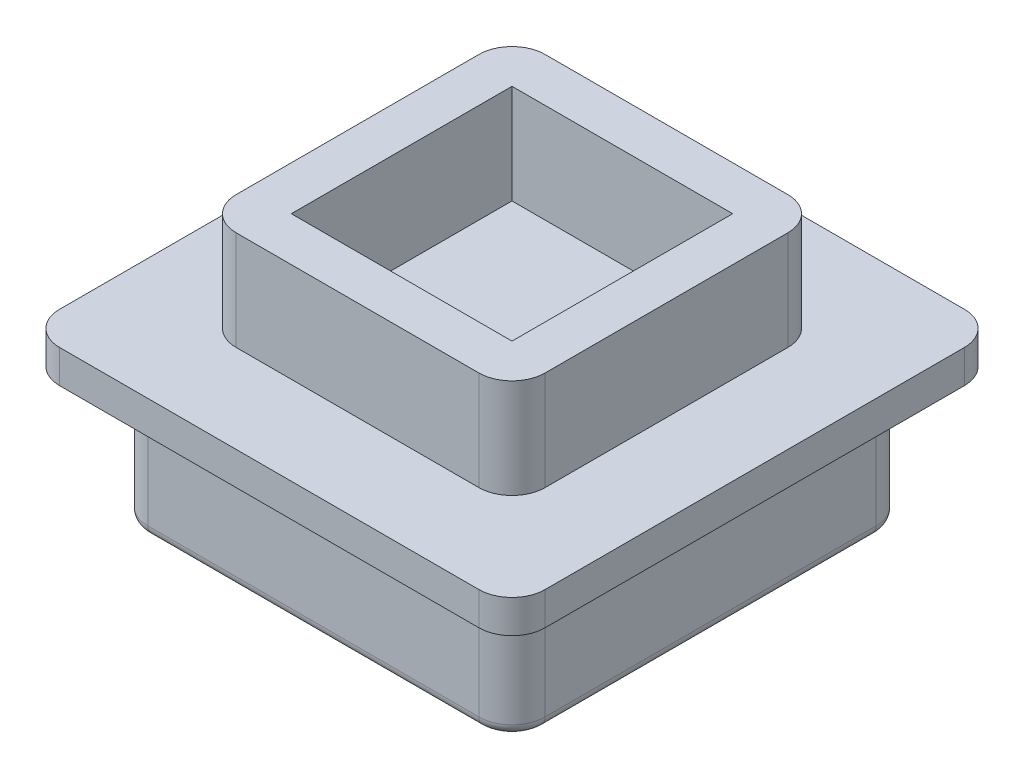
SolidWorks part; units mm, degrees
ref_plane "Front Plane" through (0, 0, 0) normal (0, 0, 1) x (1, 0, 0)
ref_plane "Top Plane" through (0, 0, 0) normal (0, 1, 0) x (1, 0, 0)
ref_plane "Right Plane" through (0, 0, 0) normal (1, 0, 0) x (0, 0, -1)
sketch "Sketch1" plane through (0, 0, 0) normal (0, 1, 0) x (1, 0, 0)
  line L1 (-4.5, -4.5) -> (4.5, -4.5)
  line L2 (-4.5, -4.5) -> (-4.5, 4.5)
  line L3 (-4.5, 4.5) -> (4.5, 4.5)
  line L4 (4.5, -4.5) -> (4.5, 4.5)
  line L5 (-4.5, -4.5) -> (4.5, 4.5) construction
  line L6 (-4.5, 4.5) -> (4.5, -4.5) construction
  point P0 (0, 0)
  dimension "D1" = 9
  dimension "D2" = 9
extrude "Boss-Extrude1" add sketch "Sketch1" along normal blind 3
sketch "Sketch2" plane through (0, 3, 0) normal (0, 1, 0) x (1, 0, 0)
  line L8 (5.5, -5.5) -> (5.5, 5.5)
  line L9 (5.5, 5.5) -> (-5.5, 5.5)
  line L10 (-5.5, 5.5) -> (-5.5, -5.5)
  line L11 (-5.5, -5.5) -> (5.5, -5.5)
  line L12 (5.5, -5.5) -> (5.5, 5.5)
  line L13 (5.5, 5.5) -> (-5.5, 5.5)
  line L14 (-5.5, 5.5) -> (-5.5, -5.5)
  line L15 (-5.5, -5.5) -> (5.5, -5.5)
  dimension "D1" = 1
extrude "Boss-Extrude2" add sketch "Sketch2" along normal blind 0.75
sketch "Sketch3" plane through (0, 3.75, 0) normal (0, 1, 0) x (1, 0, 0)
  line L0 (-3.5, 3.5) -> (3.5, 3.5)
  line L1 (-2.5, -2.5) -> (2.5, -2.5)
  line L2 (-2.5, -2.5) -> (-2.5, 2.5)
  line L3 (-2.5, 2.5) -> (2.5, 2.5)
  line L4 (2.5, -2.5) -> (2.5, 2.5)
  line L5 (-2.5, -2.5) -> (2.5, 2.5) construction
  line L6 (-2.5, 2.5) -> (2.5, -2.5) construction
  line L7 (3.5, -3.5) -> (3.5, 3.5)
  line L8 (-3.5, -3.5) -> (3.5, -3.5)
  line L9 (-3.5, -3.5) -> (-3.5, 3.5)
  point P0 (0, 0)
  dimension "D1" = 5
  dimension "D2" = 5
  dimension "D3" = 1
extrude "Boss-Extrude3" add sketch "Sketch3" along normal blind 2.25
fillet "Fillet1" radius 0.75 12 edges at (-3.5, 4.875, 3.5) (-3.5, 4.875, -3.5) (3.5, 4.875, -3.5) (3.5, 4.875, 3.5) (5.5, 3.375, 5.5) (-5.5, 3.375, 5.5) (-5.5, 3.375, -5.5) (5.5, 3.375, -5.5) (4.5, 1.5, -4.5) (-4.5, 1.5, -4.5) (-4.5, 1.5, 4.5) (4.5, 1.5, 4.5)
fillet "Fillet2" radius 0.25 8 edges at (4.2803, 0, -4.2803) (4.5, 0, 0) (4.2803, 0, 4.2803) (0, 0, 4.5) (-4.2803, 0, 4.2803) (-4.5, 0, 0) (-4.2803, 0, -4.2803) (0, 0, -4.5)
